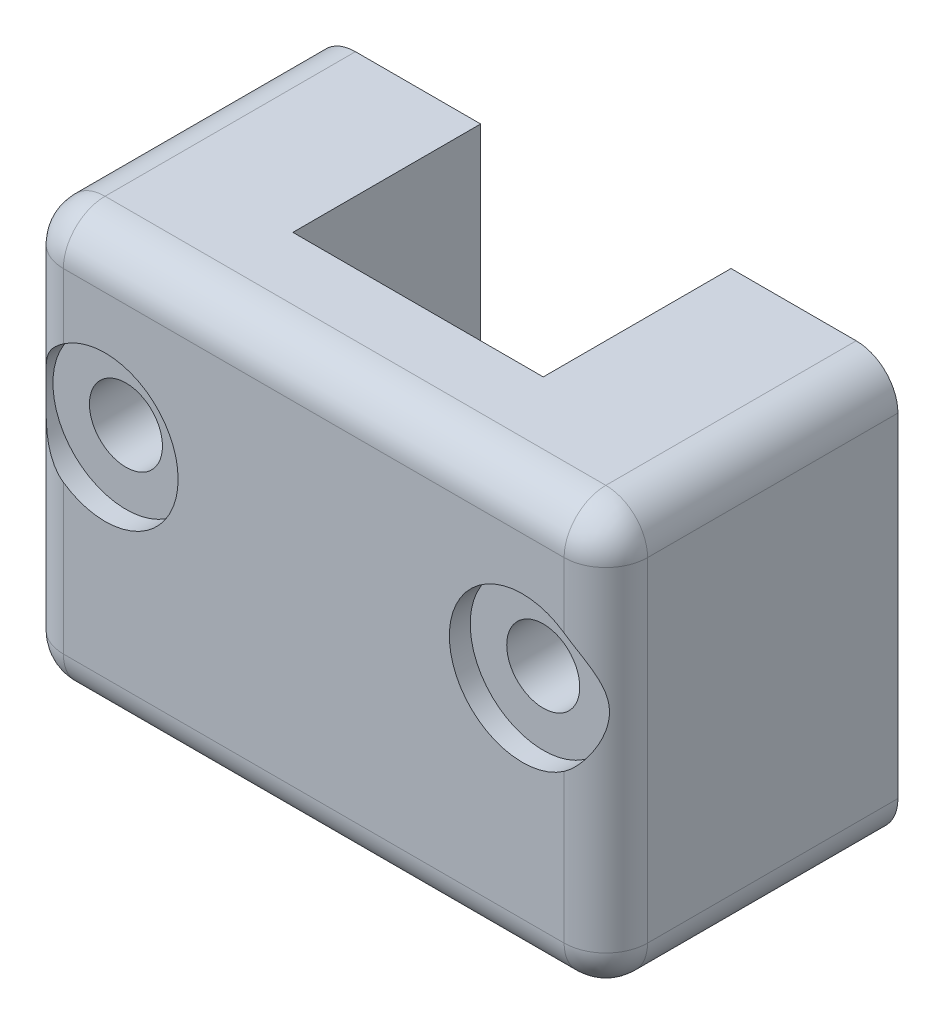
SolidWorks part; units mm, degrees
ref_plane "Front Plane" through (0, 0, 0) normal (0, 0, 1) x (1, 0, 0)
ref_plane "Top Plane" through (0, 0, 0) normal (0, 1, 0) x (1, 0, 0)
ref_plane "Right Plane" through (0, 0, 0) normal (1, 0, 0) x (0, 0, -1)
ref_plane "Plane1" through (0, -6.25, 0) normal (0, -1, 0) x (1, 0, 0)
sketch "Sketch1" plane through (0, -6.25, 0) normal (0, -1, 0) x (1, 0, 0)
  line L0 (21, 0) -> (21, 14)
  line L1 (21, 14) -> (-21, 14)
  line L2 (-21, 14) -> (-21, 0)
  line L3 (-21, 0) -> (21, 0)
extrude "Boss-Extrude1" add sketch "Sketch1" against normal blind 20
sketch "Sketch2" plane through (0, 13.75, 0) normal (0, 1, 0) x (-1, 0, 0)
  line L0 (-21, 4) -> (-10, 4)
  line L1 (-10, 4) -> (-10, 14)
  line L2 (-10, 14) -> (-21, 14)
  line L3 (-21, 14) -> (-21, 4)
extrude "Cut-Extrude1" cut sketch "Sketch2" against normal through all
sketch "Sketch3" plane through (0, 13.75, 0) normal (0, 1, 0) x (-1, 0, 0)
  line L0 (10, 4) -> (21, 4)
  line L1 (21, 4) -> (21, 14)
  line L2 (21, 14) -> (10, 14)
  line L3 (10, 14) -> (10, 4)
extrude "Cut-Extrude2" cut sketch "Sketch3" against normal through all
sketch "Sketch4" plane through (0, 13.75, 0) normal (0, 1, 0) x (-1, 0, 0)
  line L0 (-6, 0) -> (6, 0)
  line L1 (6, 0) -> (6, 10)
  line L2 (6, 10) -> (-6, 10)
  line L3 (-6, 10) -> (-6, 0)
extrude "Cut-Extrude3" cut sketch "Sketch4" against normal through all
hole_wizard "Ø4.0 (4) Diameter Hole1" positions "Sketch6" profile "Sketch5" hole size "Ø4.0" standard "ANSI Metric" end condition through all
sketch "Sketch6" plane through (0, 0, 4) normal (0, 0, 1) x (1, 0, 0)
  point P0 (15, 0)
  point P1 (-15, 0)
sketch "Sketch5" plane through (15, 0, 4) normal (1, 0, 0) x (0, -1, 0)
  line L0 (0, 0) -> (0, 4)
  line L1 (0, 4) -> (2, 4)
  line L2 (2, 4) -> (2, 0)
  line L5 (2, 0) -> (0, 0)
  line L11 (0, -6.35) -> (0, 107.95) construction
  dimension "Thru Hole Dia." = 4
  dimension "Thru Hole Depth" = 4
fillet "Fillet1" radius 1 4 edges at (21, 13.75, 2) (21, -6.25, 2) (-21, -6.25, 2) (-21, 13.75, 2) tangent propagation no
sketch "Sketch7" plane through (0, 0, 0) normal (0, 0, -1) x (-1, 0, 0)
  line L1 (-23.671, 7.8526) -> (29.4643, 7.8526)
  line L2 (-23.671, 7.8526) -> (-23.671, -10.1609)
  line L3 (-23.671, -10.1609) -> (29.4643, -10.1609)
  line L4 (29.4643, 7.8526) -> (29.4643, -10.1609)
extrude "Cut-Extrude4" cut sketch "Sketch7" against normal blind 1.5
sketch "Sketch8" plane through (0, 0, 10) normal (0, 0, -1) x (-1, 0, 0)
  line L1 (-6, 6.25) -> (6, 6.25)
  line L2 (-6, 6.25) -> (-6, -6.25)
  line L3 (-6, -6.25) -> (6, -6.25)
  line L4 (6, 6.25) -> (6, -6.25)
extrude "Cut-Extrude5" cut sketch "Sketch8" against normal blind 1.5
sketch "Sketch9" plane through (0, 0, 14) normal (0, 0, 1) x (1, 0, 0)
  line L1 (-10, 13.75) -> (10, 13.75)
  line L2 (-10, 13.75) -> (-10, -6.25)
  line L3 (-10, -6.25) -> (10, -6.25)
  line L4 (10, 13.75) -> (10, -6.25)
extrude "Boss-Extrude2" add sketch "Sketch9" along normal blind 1
sketch "Sketch10" plane through (-21, 0, 0) normal (-1, 0, 0) x (0, 0, 1)
  line L1 (1.0331, 6.5806) -> (4.5195, 6.5806)
  line L2 (1.0331, 6.5806) -> (1.0331, -7.0861)
  line L3 (1.0331, -7.0861) -> (4.5195, -7.0861)
  line L4 (4.5195, 6.5806) -> (4.5195, -7.0861)
extrude "Cut-Extrude6" cut sketch "Sketch10" against normal blind 3
sketch "Sketch11" plane through (21, 0, 0) normal (1, 0, 0) x (0, 0, -1)
  line L1 (-4.6416, 6.4935) -> (-0.2835, 6.4935)
  line L2 (-4.6416, 6.4935) -> (-4.6416, -7.0164)
  line L3 (-4.6416, -7.0164) -> (-0.2835, -7.0164)
  line L4 (-0.2835, 6.4935) -> (-0.2835, -7.0164)
extrude "Cut-Extrude7" cut sketch "Sketch11" against normal blind 3
sketch "Sketch14" plane through (0, 0, 1.5) normal (0, 0, -1) x (-1, 0, 0)
  line L1 (6, 6.25) -> (18, 6.25)
  line L2 (6, 6.25) -> (6, -6.25)
  line L3 (6, -6.25) -> (18, -6.25)
  line L4 (18, 6.25) -> (18, -6.25)
  line L5 (-6, 6.25) -> (-18, 6.25)
  line L6 (-6, 6.25) -> (-6, -6.25)
  line L7 (-6, -6.25) -> (-18, -6.25)
  line L8 (-18, 6.25) -> (-18, -6.25)
  circle A0 centre (-15, 0) radius 2
  circle A1 centre (15, 0) radius 2
extrude "Boss-Extrude3" add sketch "Sketch14" along normal blind 0.5
fillet "Fillet7" radius 3 3 edges at (-18, -6.25, 2.5) (-18, 6.25, 1.25) (18, -6.25, 2.5)
sketch "Sketch15" plane through (0, 0, 15) normal (0, 0, 1) x (1, 0, 0)
  line L0 (-10, -6.25) -> (-15, -6.25) construction
  line L1 (-10, 13.75) -> (-14, 13.75)
  line L2 (-10, 13.75) -> (-10, -6.25)
  line L3 (-10, -6.25) -> (-14, -6.25)
  line L4 (-14, 13.75) -> (-14, -6.25)
  line L5 (15, -6.25) -> (10, -6.25) construction
  line L6 (10, 13.75) -> (14, 13.75)
  line L7 (10, 13.75) -> (10, -6.25)
  line L8 (10, -6.25) -> (14, -6.25)
  line L9 (14, 13.75) -> (14, -6.25)
  dimension "D1" = 4
  dimension "D2" = 4
extrude "Boss-Extrude4" add sketch "Sketch15" against normal up to surface (14 mm away) up to face at (-13.2071, 0, 1)
sketch "Sketch16" plane through (0, 0, 15) normal (0, 0, 1) x (1, 0, 0)
  line L1 (14, 13.75) -> (27.9255, 13.75)
  line L2 (14, 13.75) -> (14, -7.5424)
  line L3 (14, -7.5424) -> (27.9255, -7.5424)
  line L4 (27.9255, 13.75) -> (27.9255, -7.5424)
  line L5 (-14, 13.75) -> (-23.8973, 13.75)
  line L6 (-14, 13.75) -> (-14, -7.995)
  line L7 (-14, -7.995) -> (-23.8973, -7.995)
  line L8 (-23.8973, 13.75) -> (-23.8973, -7.995)
extrude "Cut-Extrude8" cut sketch "Sketch16" against normal through all
sketch "Sketch17" plane through (0, 0, 10) normal (0, 0, -1) x (-1, 0, 0)
  line L1 (-6, 13.75) -> (6, 13.75)
  line L2 (-6, 13.75) -> (-6, 6.25)
  line L3 (-6, 6.25) -> (6, 6.25)
  line L4 (6, 13.75) -> (6, 6.25)
extrude "Cut-Extrude9" cut sketch "Sketch17" against normal up to surface (1.5 mm away) up to face at (0, 0, 11.5)
sketch "Sketch18" plane through (0, 7.8526, 0) normal (0, -1, 0) x (-1, 0, 0)
  line L1 (14, -1) -> (-15.147, -1)
  line L2 (14, -1) -> (14, 1.1748)
  line L3 (14, 1.1748) -> (-15.147, 1.1748)
  line L4 (-15.147, -1) -> (-15.147, 1.1748)
extrude "Cut-Extrude10" cut sketch "Sketch18" against normal up to surface (5.8974 mm away) up to face at (0, 13.75, 6.625)
sketch "Sketch19" plane through (0, 0, 11.5) normal (0, 0, -1) x (-1, 0, 0)
  line L1 (-6, 13.75) -> (6, 13.75)
  line L2 (-6, 13.75) -> (-6, -6.25)
  line L3 (-6, -6.25) -> (6, -6.25)
  line L4 (6, 13.75) -> (6, -6.25)
extrude "Boss-Extrude5" add sketch "Sketch19" along normal blind 1.5
sketch "Sketch20" plane through (0, 0, 1) normal (0, 0, -1) x (-1, 0, 0)
  line L1 (-10, 7.8526) -> (-6, 7.8526)
  line L2 (-10, 7.8526) -> (-10, 6.25)
  line L3 (-10, 6.25) -> (-6, 6.25)
  line L4 (-6, 7.8526) -> (-6, 6.25)
  line L5 (6, 7.8526) -> (10, 7.8526)
  line L6 (6, 7.8526) -> (6, 6.25)
  line L7 (6, 6.25) -> (10, 6.25)
  line L8 (10, 7.8526) -> (10, 6.25)
extrude "Boss-Extrude6" add sketch "Sketch20" against normal blind 1.5
sketch "Sketch24" plane through (0, 0, 1) normal (0, 0, -1) x (-1, 0, 0)
  line L0 (-10, 13.75) -> (-10, -6.25) construction
  line L1 (-6, 13.75) -> (-14, 13.75) construction
  line L2 (-14, -6.25) -> (-6, -6.25) construction
  line L3 (-10, -6.25) -> (10, -6.25) construction
  line L4 (6, -6.25) -> (14, -6.25) construction
  line L5 (10, -6.25) -> (10, 13.75) construction
  line L6 (14, 13.75) -> (6, 13.75) construction
  circle A0 centre (-10, 5.75) radius 1.75
  circle A1 centre (10, 5.75) radius 1.75
  dimension "D1" = 3.5
  dimension "D2" = 3.5
  dimension "D3" = 8
  dimension "D4" = 8
extrude "Cut-Extrude11" cut sketch "Sketch24" against normal up to surface (14 mm away) up to face at (0, 3.75, 15)
sketch "Sketch25" plane through (0, 0, 15) normal (0, 0, 1) x (1, 0, 0)
  circle A0 centre (10, 5.75) radius 3.5
  circle A1 centre (-10, 5.75) radius 3.5
  dimension "D1" = 7
  dimension "D2" = 7
extrude "Cut-Extrude12" cut sketch "Sketch25" against normal blind 1
fillet "Fillet8" radius 2 8 edges at (0, 13.75, 15) (0, -6.25, 15) (14, -6.25, 8) (14, 13.75, 8) (-14, 13.75, 8) (-14, 3.75, 15) (-14, -6.25, 8) (14, 3.75, 15)
